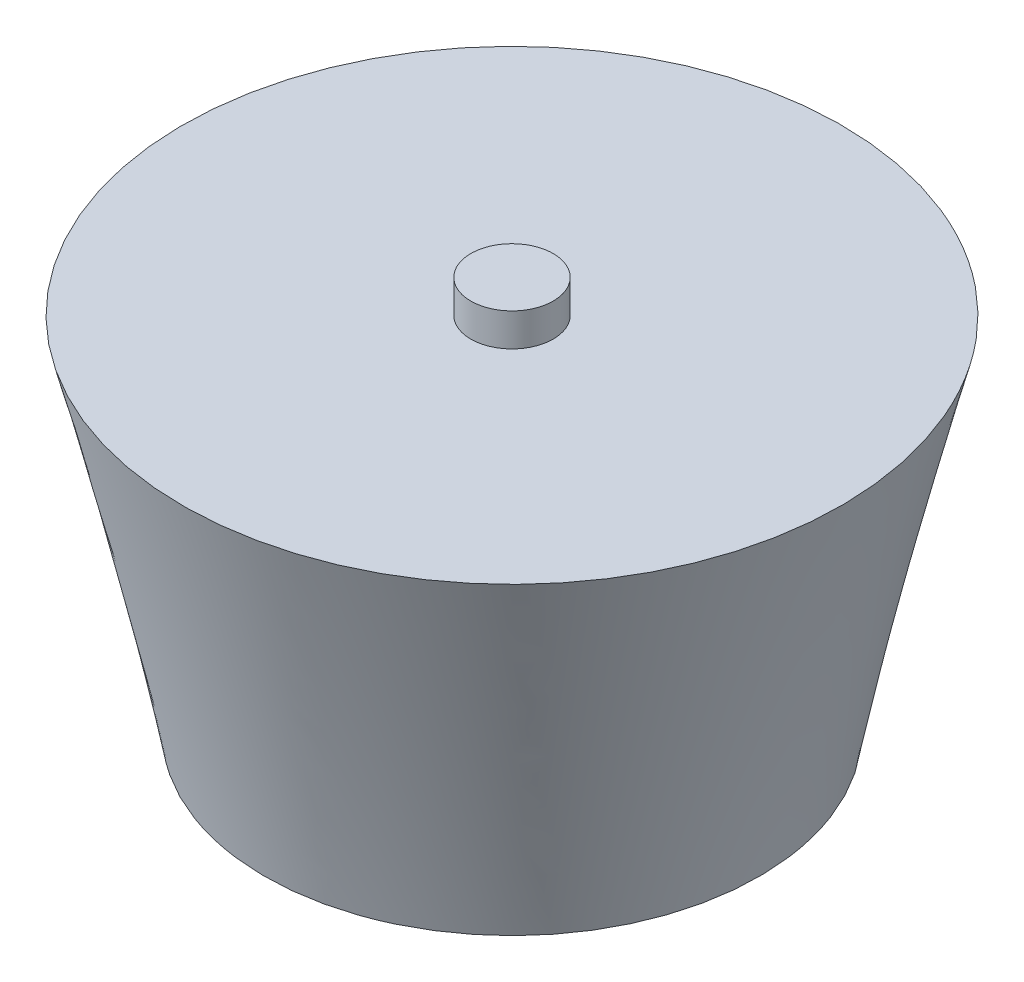
SolidWorks part; units mm, degrees
material "Rubber"
ref_plane "Front Plane" through (0, 0, 0) normal (0, 0, 1) x (1, 0, 0)
ref_plane "Top Plane" through (0, 0, 0) normal (0, 1, 0) x (1, 0, 0)
ref_plane "Right Plane" through (0, 0, 0) normal (1, 0, 0) x (0, 0, -1)
sketch "Sketch1" plane through (0, 0, 0) normal (0, 1, 0) x (1, 0, 0)
  circle A0 centre (0, 0) radius 15
  dimension "D1" = 30
ref_plane "Plane1" through (0, 22, 0) normal (0, 1, 0) x (1, 0, 0)
sketch "Sketch2" plane through (0, 22, 0) normal (0, 1, 0) x (1, 0, 0)
  circle A0 centre (0, 0) radius 20
  dimension "D1" = 40
loft "Loft1" add profiles "Sketch2", "Sketch1" connector at (-14.0082, 22, 14.2748) connector at (-6.751, 0, 13.3949)
sketch "Sketch3" plane through (0, 22, 0) normal (0, 1, 0) x (1, 0, 0)
  circle A0 centre (0, 0) radius 2.5
  dimension "D1" = 5
extrude "Boss-Extrude1" add sketch "Sketch3" along normal blind 2
